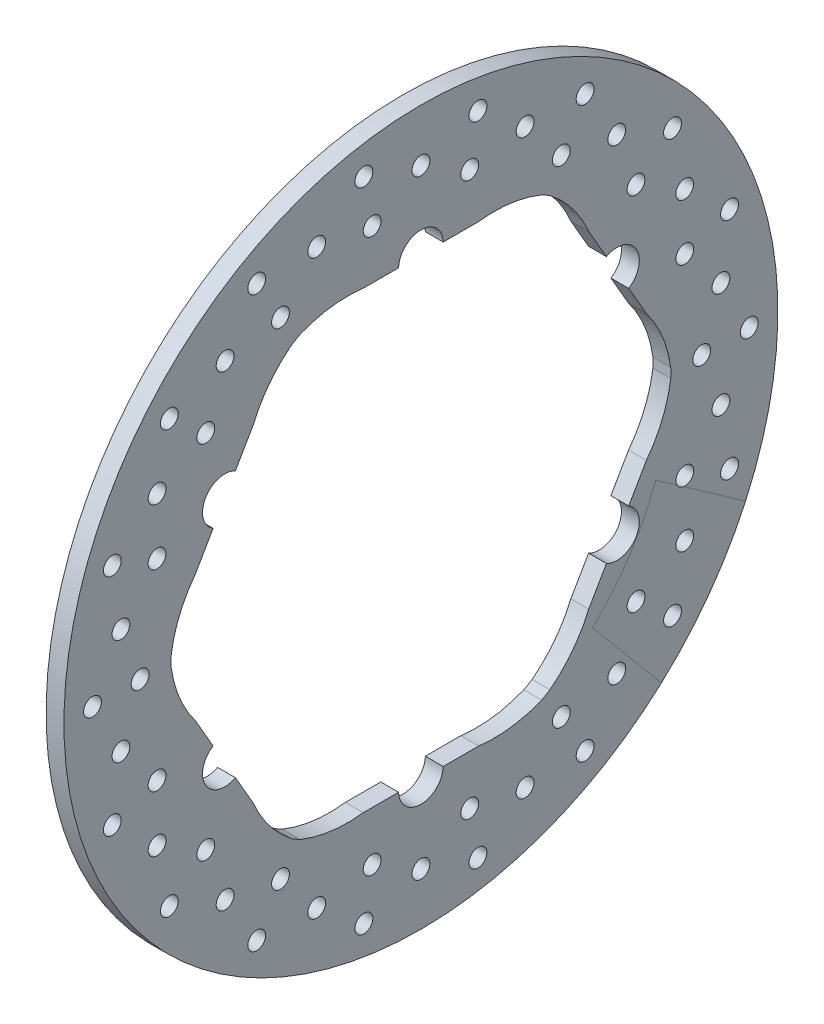
SolidWorks part; units mm, degrees
material "Gray Cast Iron (w/YS)"
ref_plane "X-Y Datum" through (0, 0, 0) normal (0, 0, 1) x (1, 0, 0)
ref_plane "X-Z Datum" through (0, 0, 0) normal (0, 1, 0) x (1, 0, 0)
ref_plane "Y-Z Datum" through (0, 0, 0) normal (1, 0, 0) x (0, 0, -1)
sketch "Sketch1" plane through (0, 0, 0) normal (1, 0, 0) x (0, 0, -1)
  circle A0 centre (0, 0) radius 95.25
  circle A1 centre (0, 0) radius 66.675
  dimension "D1" = 190.5
  dimension "D2" = 133.35
extrude "Main Rotor" add sketch "Sketch1" along normal blind 4.7625
sketch "Sketch2" plane through (4.7625, 0, 0) normal (1, 0, 0) x (0, 0, -1)
  line L0 (0, 0) -> (-50000, 0) construction
  line L1 (0, 0) -> (-93.8029, 16.54) construction
  line L4 (-82.3453, 29.9712) -> (-70.4112, 25.6276) construction
  circle A2 centre (0, 0) radius 95.25 construction
  circle A72 centre (-80.0452, 14.1141) radius 2.3813
  circle A73 centre (0, 0) radius 66.675 construction
  circle A74 centre (-82.3453, 29.9712) radius 2.3812
  circle A75 centre (-70.4112, 25.6276) radius 2.3813
  circle A76 centre (0, 0) radius 95.25 construction
  circle A77 centre (-70.3905, 40.64) radius 2.3812
  circle A78 centre (-67.1285, 56.3275) radius 2.3813
  circle A79 centre (0, 0) radius 66.675 construction
  circle A80 centre (-57.3997, 48.1641) radius 2.3813
  circle A81 centre (-52.2458, 62.2641) radius 2.3813
  circle A82 centre (-87.63, 0) radius 2.3813
  circle A83 centre (-43.815, 75.8898) radius 2.3812
  circle A84 centre (-37.465, 64.8913) radius 2.3813
  circle A85 centre (-74.93, 0) radius 2.3813
  circle A86 centre (-27.7994, 76.3782) radius 2.3812
  circle A87 centre (-15.2168, 86.2987) radius 2.3813
  circle A88 centre (-13.0115, 73.7916) radius 2.3813
  circle A89 centre (0, 81.28) radius 2.3813
  circle A90 centre (15.2168, 86.2987) radius 2.3813
  circle A91 centre (13.0115, 73.7916) radius 2.3813
  circle A92 centre (27.7994, 76.3782) radius 2.3813
  circle A93 centre (43.815, 75.8898) radius 2.3813
  circle A94 centre (37.465, 64.8913) radius 2.3813
  circle A95 centre (52.2458, 62.2641) radius 2.3813
  circle A96 centre (67.1285, 56.3275) radius 2.3813
  circle A97 centre (57.3997, 48.1641) radius 2.3813
  circle A98 centre (70.3905, 40.64) radius 2.3812
  circle A99 centre (82.3453, 29.9712) radius 2.3813
  circle A100 centre (70.4112, 25.6276) radius 2.3813
  circle A101 centre (80.0452, 14.1141) radius 2.3813
  circle A102 centre (87.63, 0) radius 2.3813
  circle A103 centre (74.93, 0) radius 2.3813
  circle A104 centre (80.0452, -14.1141) radius 2.3813
  circle A105 centre (82.3453, -29.9712) radius 2.3812
  circle A106 centre (70.4112, -25.6276) radius 2.3812
  circle A107 centre (70.3905, -40.64) radius 2.3813
  circle A108 centre (67.1285, -56.3275) radius 2.3812
  circle A109 centre (57.3997, -48.1641) radius 2.3813
  circle A110 centre (52.2458, -62.2641) radius 2.3812
  circle A111 centre (43.815, -75.8898) radius 2.3813
  circle A112 centre (37.465, -64.8913) radius 2.3813
  circle A113 centre (27.7994, -76.3782) radius 2.3813
  circle A114 centre (15.2168, -86.2987) radius 2.3813
  circle A115 centre (13.0115, -73.7916) radius 2.3812
  circle A116 centre (0, -81.28) radius 2.3812
  circle A117 centre (-15.2168, -86.2987) radius 2.3813
  circle A118 centre (-13.0115, -73.7916) radius 2.3813
  circle A119 centre (-27.7994, -76.3782) radius 2.3812
  circle A120 centre (-43.815, -75.8898) radius 2.3813
  circle A121 centre (-37.465, -64.8913) radius 2.3813
  circle A122 centre (-52.2458, -62.2641) radius 2.3813
  circle A123 centre (-67.1285, -56.3275) radius 2.3813
  circle A124 centre (-57.3997, -48.1641) radius 2.3813
  circle A125 centre (-70.3905, -40.64) radius 2.3813
  circle A126 centre (-82.3453, -29.9712) radius 2.3813
  circle A127 centre (-70.4112, -25.6276) radius 2.3813
  circle A128 centre (-80.0452, -14.1141) radius 2.3813
  point P109 (0, 0)
  dimension "D1" = 4.7625
  dimension "D2" = 12.7
  dimension "D3" = 10
  dimension "D5" = 81.28
  dimension "D4" = 87.63
  dimension "D6" = 18
extrude "Cut Slots" cut sketch "Sketch2" against normal through all
sketch "Sketch3" plane through (4.7625, 0, 0) normal (1, 0, 0) x (0, 0, -1)
  line L0 (0.3454, 5.0869) -> (-47951.5604, 14168.94) construction
  line L1 (0, 21.2491) -> (-18.4023, 10.6246)
  line L2 (-18.4023, 10.6246) -> (-18.4023, -10.6246)
  line L3 (-18.4023, -10.6246) -> (0, -21.2491)
  line L4 (0, -21.2491) -> (18.4023, -10.6246)
  line L5 (18.4023, -10.6246) -> (18.4023, 10.6246)
  line L6 (18.4023, 10.6246) -> (0, 21.2491)
  line L7 (0, 0) -> (43301.2702, 25000) construction
  line L8 (0, 0) -> (0, 50000) construction
  line L12 (9.525, -59.2994) -> (-9.525, -59.2994) construction
  line L17 (-30.6007, -53.002) -> (24969.3838, 43248.2414) construction
  line L18 (-60.783, 0) -> (49939.217, 0) construction
  line L19 (0, 0) -> (-25000, 43301.2702) construction
  line L20 (-14.2015, 9.3837) -> (0, 17.583) construction
  line L21 (-1.5875, 20.3326) -> (-2.825, 22.476) construction
  arc A0 (8.6043, -53.0208) -> (15.2264, -60.5686) centre (16.2243, -53.0143) ccw
  circle A1 centre (0, 0) radius 66.675 construction
  arc A7 (-15.2264, -60.5686) -> (-32.2316, -58.3668) centre (-19.5921, -27.5182) cw
  arc A10 (15.2264, -60.5686) -> (32.2316, -58.3668) centre (19.5921, -27.5182) ccw
  arc A19 (-19.6024, -33.9524) -> (-8.6043, -53.0208) centre (-30.6006, -53.0019) cw
  arc A25 (41.6152, -33.9619) -> (44.8408, -43.4707) centre (37.7996, -40.5577) cw
  arc A26 (34.4313, -57.0968) -> (66.6629, -1.27) centre (0, 0) ccw
  arc A27 (50.2195, -19.0589) -> (60.0672, -17.0979) centre (54.0238, -12.4565) ccw
  arc A28 (19.6024, -33.9524) -> (8.6043, -53.0208) centre (30.6006, -53.0019) ccw
  arc A29 (60.0672, 17.0979) -> (50.2195, 19.0589) centre (54.0238, 12.4565) ccw
  arc A30 (-44.8408, -43.4707) -> (-34.4313, -57.0968) centre (-14.0354, -30.7264) ccw
  arc A31 (-19.6024, -33.9524) -> (-41.6152, -33.9619) centre (-30.6006, -53.0019) ccw
  arc A32 (-39.2049, 0) -> (-50.2195, -19.0589) centre (-61.2013, 0) cw
  arc A33 (-60.0672, -17.0979) -> (-66.6629, -1.27) centre (-33.6275, 3.2082) cw
  arc A34 (-60.0672, 17.0979) -> (-66.6629, 1.27) centre (-33.6275, -3.2082) ccw
  arc A35 (44.8408, 43.4707) -> (41.6152, 33.9619) centre (37.7996, 40.5577) cw
  arc A36 (-32.2316, -58.3668) -> (32.2316, -58.3668) centre (0, 0) ccw
  arc A37 (15.2264, 60.5686) -> (8.6043, 53.0208) centre (16.2243, 53.0143) ccw
  arc A38 (-8.6043, 53.0208) -> (-15.2264, 60.5686) centre (-16.2243, 53.0143) ccw
  arc A39 (-44.8408, 43.4707) -> (-41.6152, 33.9619) centre (-37.7996, 40.5577) ccw
  arc A40 (-50.2195, 19.0589) -> (-60.0672, 17.0979) centre (-54.0238, 12.4565) ccw
  arc A41 (-50.2195, -19.0589) -> (-60.0672, -17.0979) centre (-54.0238, -12.4565) cw
  arc A42 (-8.6043, -53.0208) -> (-15.2264, -60.5686) centre (-16.2243, -53.0143) cw
  arc A43 (-41.6152, -33.9619) -> (-44.8408, -43.4707) centre (-37.7996, -40.5577) ccw
  arc A44 (-39.2049, 0) -> (-50.2195, 19.0589) centre (-61.2013, 0) ccw
  arc A45 (-19.6025, 33.9524) -> (-41.6152, 33.9619) centre (-30.6007, 53.0019) cw
  arc A46 (-44.8408, 43.4707) -> (-34.4313, 57.0968) centre (-14.0354, 30.7264) cw
  arc A47 (-15.2264, 60.5686) -> (-32.2316, 58.3668) centre (-19.5921, 27.5182) ccw
  arc A48 (-19.6025, 33.9524) -> (-8.6043, 53.0208) centre (-30.6007, 53.0019) ccw
  arc A49 (19.6024, 33.9524) -> (8.6043, 53.0208) centre (30.6006, 53.0019) cw
  arc A50 (15.2264, 60.5686) -> (32.2316, 58.3668) centre (19.5921, 27.5182) cw
  arc A51 (44.8408, 43.4707) -> (34.4313, 57.0968) centre (14.0354, 30.7264) ccw
  arc A52 (19.6024, 33.9524) -> (41.6152, 33.9619) centre (30.6006, 53.0019) ccw
  arc A53 (39.2049, 0) -> (50.2195, 19.0589) centre (61.2013, 0) cw
  arc A54 (60.0672, 17.0979) -> (66.6629, 1.27) centre (33.6275, -3.2082) cw
  arc A55 (60.0672, -17.0979) -> (66.6629, -1.27) centre (33.6275, 3.2082) ccw
  arc A56 (39.2049, 0) -> (50.2195, -19.0589) centre (61.2013, 0) ccw
  arc A57 (19.6024, -33.9524) -> (41.6152, -33.9619) centre (30.6007, -53.0019) cw
  arc A58 (44.8408, -43.4707) -> (34.4313, -57.0968) centre (14.0354, -30.7264) cw
  circle A59 centre (0, 20.3326) radius 1.5875
  arc A60 (-66.6629, -1.27) -> (-34.4313, -57.0968) centre (0, 0) ccw
  arc A62 (-34.4313, 57.0968) -> (-66.6629, 1.27) centre (0, 0) ccw
  arc A64 (32.2316, 58.3668) -> (-32.2316, 58.3668) centre (0, 0) ccw
  arc A66 (66.6629, 1.27) -> (34.4313, 57.0968) centre (0, 0) ccw
  circle A71 centre (0, 0) radius 7.4362 construction
  circle A72 centre (0, 17.583) radius 3.175 construction
  circle A73 centre (17.6086, 10.1663) radius 1.5875
  circle A74 centre (17.6086, -10.1663) radius 1.5875
  circle A75 centre (0, -20.3326) radius 1.5875
  circle A76 centre (-17.6085, -10.1663) radius 1.5875
  circle A77 centre (-17.6085, 10.1663) radius 1.5875
  point P34 (0, -59.2994)
  point P35 (-9.2012, 15.9369)
  point P116 (0, 0)
  point P124 (0, 0)
  dimension "D2" = 42.799
  dimension "D4" = 7.62
  dimension "D7" = 1.27
  dimension "D8" = 33.3375
  dimension "D9" = 21.9964
  dimension "D10" = 3.175
  dimension "D11" = 3.175
  dimension "D12" = 6.35
  dimension "D13" = 6
  dimension "D1" = 36.8046
  dimension "D3" = 6
  dimension "D6" = 19.05
extrude "Boss-Extrude2" add sketch "Sketch3" against normal up to surface (4.7625 mm away) contours A54 A66 A51 A35 A52 A49 A37 A50 A64 A47 A38 A48 A45 A39 A46 A62 A34 A40 A44 A32 A41 A33 A60 A30 A43 A31 A19 A42 A7 A36 A10 A0 A28 A57 A25 A58 A26 A55 A27 A56 A53 A29 L1 A59 L6 L5 L4 region at (4.7625, -59.2833, -9.0788) up to face at (0, 0, 85.2488)
fillet "Fillet1" [suppressed] radius 3.175
sketch "Sketch4" plane through (0, 0, 0) normal (-1, 0, 0) x (0, 0, 1)
  circle A0 centre (0, 45.212) radius 1.27
  circle A1 centre (39.1547, 22.606) radius 1.27
  circle A2 centre (39.1547, -22.606) radius 1.27
  circle A3 centre (0, -45.212) radius 1.27
  circle A4 centre (-39.1547, -22.606) radius 1.27
  circle A5 centre (-39.1547, 22.606) radius 1.27
  point P16 (0, 0)
  dimension "D1" = 45.212
  dimension "D2" = 2.54
  dimension "D3" = 6
extrude "Cut-Extrude2" cut sketch "Sketch4" against normal through all
sketch "Sketch5" plane through (4.7625, 0, 0) normal (1, 0, 0) x (0, 0, -1)
  line L0 (0, 0) -> (-50000, 0) construction
  line L1 (0, 0) -> (-46984.631, 17101.0072) construction
  line L2 (62.654, -22.8042) -> (86.6311, -39.5931)
  line L3 (45.7933, -48.4616) -> (64.1833, -70.378)
  circle A0 centre (0, 0) radius 95.25 construction
  circle A1 centre (0, 0) radius 66.675 construction
  arc A2 (64.1833, -70.378) -> (86.6311, -39.5931) centre (0, 0) ccw
  arc A3 (45.7933, -48.4616) -> (62.654, -22.8042) centre (0, 0) ccw
  dimension "D1" = 20
  dimension "D2" = 15
  dimension "D3" = 15
  dimension "D4" = 38.1
split line "Split Line1"
ref_axis "Axis1" through (5.0006, 0, 0) along (-1, 0, 0)
sketch "Sketch6" plane through (4.7625, 0, 0) normal (1, 0, 0) x (0, 0, -1)
  line L0 (0, 0) -> (53.7487, 0) construction
  line L1 (0, 43.8283) -> (0, 9.5266) construction
  line L2 (-25.1315, 60.4139) -> (26.8555, 60.4139) construction
  line L3 (-18.4023, 60.5917) -> (-5.9505, 60.5917)
  line L4 (5.9505, 60.5917) -> (18.4023, 60.5917)
  line L5 (-18.4023, 60.5917) -> (-18.4023, 35.1917)
  line L6 (-18.4023, 35.1917) -> (18.4023, 35.1917)
  line L7 (18.4023, 35.1917) -> (18.4023, 60.5917)
  arc A0 (5.9505, 60.5917) -> (-5.9505, 60.5917) centre (0, 60.4139) ccw
  dimension "D2" = 11.9062
  dimension "D1" = 60.4139
  dimension "D3" = 0.3556
  dimension "D4" = 36.8046
  dimension "D5" = 25.4
extrude "FE12 Cut OUt" cut sketch "Sketch6" against normal up to surface (4.7625 mm away) up to face at (0, 0, 0)
pattern_circular "CirPattern1" count 6 over 360 about axis through (4.7625, 0, 0) along (-1, 0, 0) of "FE12 Cut OUt"
sketch "Sketch7" plane through (4.7625, 0, 0) normal (1, 0, 0) x (0, 0, -1)
  circle A0 centre (0, 0) radius 46.99
  dimension "D1" = 93.98
extrude "Cleanup Cut" cut sketch "Sketch7" against normal through all
